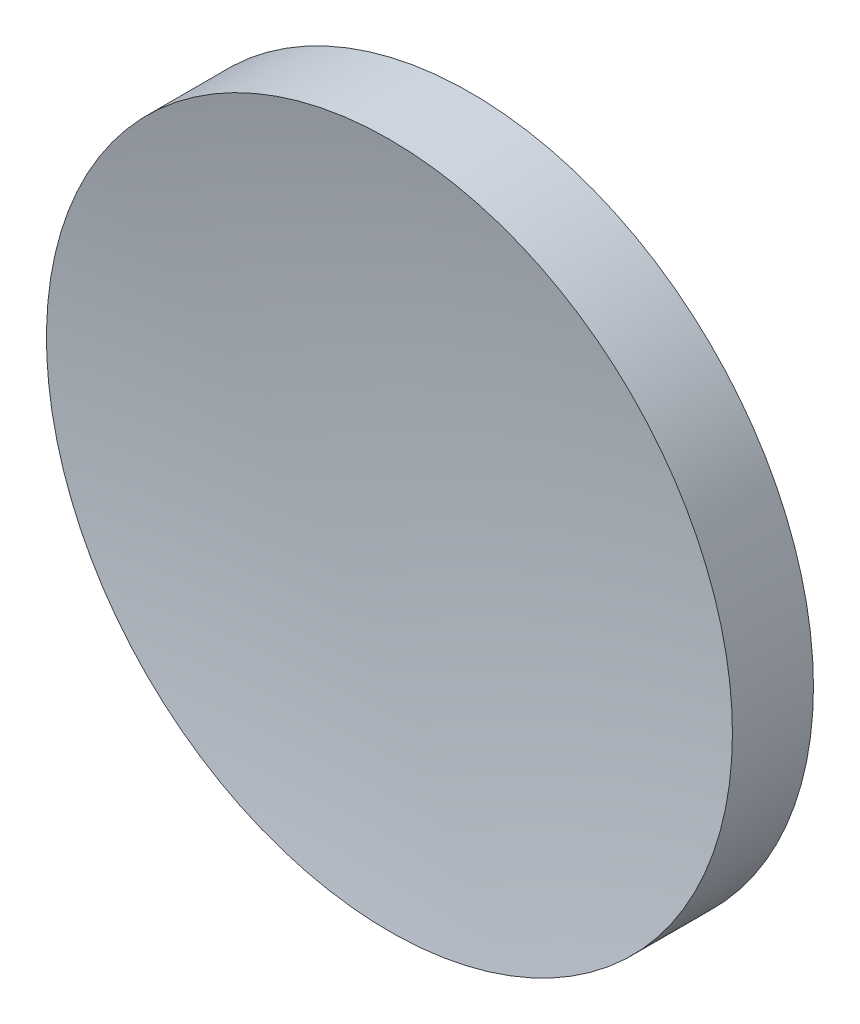
SolidWorks part; units mm, degrees
ref_plane "前视基准面" through (0, 0, 0) normal (0, 0, 1) x (1, 0, 0)
ref_plane "上视基准面" through (0, 0, 0) normal (0, 1, 0) x (1, 0, 0)
ref_plane "右视基准面" through (0, 0, 0) normal (1, 0, 0) x (0, 0, -1)
sketch "草图1" plane through (0, 0, 0) normal (0, 0, 1) x (1, 0, 0)
  circle A0 centre (0, 0) radius 12.7
extrude "凸台-拉伸1" add sketch "草图1" along normal blind 3
sketch "草图2" plane through (0, 0, 0) normal (1, 0, 0) x (0, 0, -1)
  line L0 (-1.8063, 0) -> (0, 0)
  line L1 (-1.8063, 0) -> (-69.9616, 0)
  line L3 (-69.9616, 0) -> (-138.1168, 0)
  circle A0 centre (-69.9616, 0) radius 68.1553
revolve "切除-旋转4" cut sketch "草图2" angle 360 about L0 region at (0, 28.926, 69.9616)
